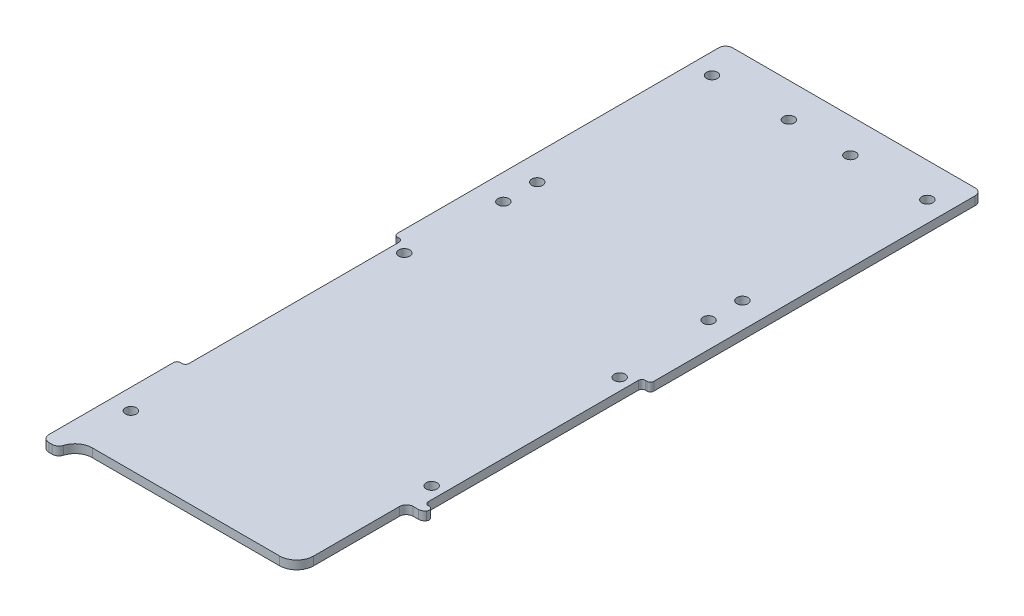
SolidWorks part; units mm, degrees
ref_plane "Front Plane" through (0, 0, 0) normal (0, 0, 1) x (1, 0, 0)
ref_plane "Top Plane" through (0, 0, 0) normal (0, 1, 0) x (1, 0, 0)
ref_plane "Right Plane" through (0, 0, 0) normal (1, 0, 0) x (0, 0, -1)
sketch "Sketch1" plane through (0, 0, 0) normal (0, 1, 0) x (1, 0, 0)
  line L0 (-39.9997, 0) -> (-39.9997, 114.3) construction
  line L1 (-47.625, 127) -> (47.625, 127)
  line L2 (-47.625, 127) -> (-47.625, -127)
  line L3 (-47.625, -127) -> (47.625, -127)
  line L4 (47.625, 127) -> (47.625, -127)
  line L5 (-47.625, 127) -> (47.625, -127) construction
  line L6 (-47.625, -127) -> (47.625, 127) construction
  line L7 (0, 0) -> (0, 127) construction
  line L8 (-39.9997, 0) -> (-39.9997, -101.6) construction
  line L9 (-39.9997, 0) -> (0, 0) construction
  line L10 (-41.275, -127) -> (-41.275, -120.65)
  line L11 (-41.275, -120.65) -> (41.275, -120.65)
  line L12 (41.275, -120.65) -> (41.275, -127)
  line L13 (-39.9997, 114.3) -> (-11.4247, 114.3) construction
  line L14 (39.9997, 114.3) -> (11.4247, 114.3) construction
  circle A0 centre (-39.9997, 114.3) radius 2.032
  circle A1 centre (-39.9997, 0) radius 2.032
  circle A2 centre (-39.9997, -101.6) radius 2.032
  circle A3 centre (39.9997, -101.6) radius 2.032
  circle A4 centre (39.9997, 0) radius 2.032
  circle A5 centre (39.9997, 114.3) radius 2.032
  circle A6 centre (-11.4247, 114.3) radius 2.032
  circle A7 centre (11.4247, 114.3) radius 2.032
  circle A8 centre (-39.9997, -69.85) radius 2.032
  circle A9 centre (39.9997, -69.85) radius 2.032
  point P0 (0, 0)
  dimension "D4" = 4.064
  dimension "D10" = 28.575
  dimension "D1" = 95.25
  dimension "D2" = 254
  dimension "D3" = 7.6253
  dimension "D5" = 12.7
  dimension "D6" = 25.4
  dimension "D7" = 6.35
  dimension "D8" = 6.35
  dimension "D9" = 6.35
  dimension "D11" = 69.85
extrude "Boss-Extrude1" add sketch "Sketch1" along normal blind 3.175 contours L4 L1 L2 L3 A4 A0 A1 A2 A3 A5 | A8 | A3 region at (0, 0, -2.6944) region at (39.9997, 0, 101.6) region at (-39.9997, 0, 69.85)
fillet "Fillet1" radius 2.54 4 edges at (-47.625, 1.5875, -127) (47.625, 1.5875, -127) (47.625, 1.5875, 127) (-47.625, 1.5875, 127)
fillet "Fillet2" radius 2.54 2 edges at (41.275, 1.5875, 127) (-41.275, 1.5875, 127)
fillet "Fillet3" radius 6.35 2 edges at (41.275, 1.5875, 120.65) (-41.275, 1.5875, 120.65)
sketch "Sketch2" plane through (0, 0, 0) normal (0, -1, 0) x (1, 0, 0)
  line L1 (43.815, 127) -> (45.085, 127) construction
  line L2 (40.6451, 123.5787) -> (40.6451, 79.8881)
  line L3 (40.6451, 79.8881) -> (47.625, 79.8881)
  line L11 (47.625, -124.46) -> (47.625, 124.46) construction
  line L12 (43.815, 127) -> (45.085, 127)
  line L13 (47.625, 79.8881) -> (47.625, 124.46)
  arc A0 (35.2956, 120.65) -> (41.3809, 125.1857) centre (35.2956, 127) ccw construction
  arc A1 (43.815, 127) -> (41.3809, 125.1857) centre (43.815, 124.46) ccw construction
  arc A2 (47.625, 124.46) -> (45.085, 127) centre (45.085, 124.46) ccw construction
  arc A3 (40.6451, 123.5787) -> (41.3809, 125.1857) centre (35.2956, 127) ccw
  arc A4 (43.815, 127) -> (41.3809, 125.1857) centre (43.815, 124.46) ccw
  arc A5 (47.625, 124.46) -> (45.085, 127) centre (45.085, 124.46) ccw
  dimension "D2" = 47.1119
  dimension "D1" = 6.9799
extrude "Cut-Extrude1" cut sketch "Sketch2" against normal through all
fillet "Fillet4" radius 6.35 1 edges at (40.6451, 1.5875, 123.5787)
fillet "Fillet5" radius 2.54 2 edges at (47.625, 1.5875, 79.8881) (40.6451, 1.5875, 79.8881)
sketch "Sketch3" plane through (0, 0, 0) normal (0, -1, 0) x (1, 0, 0)
  line L0 (-36.3061, -49.7791) -> (-39.9129, -49.7791) construction
  line L1 (-40.4209, -49.276) -> (-40.4209, -45.7043) construction
  line L2 (-35.7981, -45.7043) -> (-35.7981, -49.276) construction
  line L3 (-39.9129, -45.2013) -> (-36.3061, -45.2013) construction
  line L4 (-36.3061, -37.2027) -> (-39.9129, -37.2027) construction
  line L5 (-35.7981, -33.1279) -> (-35.7981, -36.6996) construction
  line L6 (-40.4209, -36.6996) -> (-40.4209, -33.1279) construction
  line L7 (-39.9129, -32.6249) -> (-36.3061, -32.6249) construction
  line L8 (36.2871, -32.6249) -> (39.8939, -32.6249) construction
  line L9 (40.4019, -33.1279) -> (40.4019, -36.6996) construction
  line L10 (39.8939, -37.2027) -> (36.2871, -37.2027) construction
  line L11 (35.7791, -36.6996) -> (35.7791, -33.1279) construction
  line L12 (36.2871, -45.2013) -> (39.8939, -45.2013) construction
  line L13 (35.7791, -49.276) -> (35.7791, -45.7043) construction
  line L14 (40.4019, -45.7043) -> (40.4019, -49.276) construction
  line L15 (39.8939, -49.7791) -> (36.2871, -49.7791) construction
  line L16 (-36.3061, -49.7791) -> (-39.9129, -49.7791)
  line L17 (-40.4209, -49.276) -> (-40.4209, -45.7043)
  line L18 (-35.7981, -45.7043) -> (-35.7981, -49.276)
  line L19 (-39.9129, -45.2013) -> (-36.3061, -45.2013)
  line L20 (-36.3061, -37.2027) -> (-39.9129, -37.2027)
  line L21 (-35.7981, -33.1279) -> (-35.7981, -36.6996)
  line L22 (-40.4209, -36.6996) -> (-40.4209, -33.1279)
  line L23 (-39.9129, -32.6249) -> (-36.3061, -32.6249)
  line L24 (36.2871, -32.6249) -> (39.8939, -32.6249)
  line L25 (40.4019, -33.1279) -> (40.4019, -36.6996)
  line L26 (39.8939, -37.2027) -> (36.2871, -37.2027)
  line L27 (35.7791, -36.6996) -> (35.7791, -33.1279)
  line L28 (36.2871, -45.2013) -> (39.8939, -45.2013)
  line L29 (35.7791, -49.276) -> (35.7791, -45.7043)
  line L30 (40.4019, -45.7043) -> (40.4019, -49.276)
  line L31 (39.8939, -49.7791) -> (36.2871, -49.7791)
  line L32 (-47.625, -25.836) -> (47.625, -25.836)
  line L33 (-47.625, -124.46) -> (-47.625, 124.46) construction
  line L34 (47.625, -124.46) -> (47.625, 77.3481) construction
  line L35 (0, -25.836) -> (0, -56.0686) construction
  line L1362 (-40.4209, -34.9138) -> (-35.7981, -34.9138)
  line L1857 (-38.1095, -32.6249) -> (-38.1095, -37.2027)
  line L1858 (-38.1095, -45.2013) -> (-38.1095, -49.7791)
  line L1859 (-40.4209, -47.4902) -> (-35.7981, -47.4902)
  circle A0 centre (-38.1095, -34.9138) radius 2.032
  circle A1 centre (-38.1095, -47.4902) radius 2.032
  circle A2 centre (38.1095, -47.4902) radius 2.032
  circle A3 centre (38.1095, -34.9138) radius 2.032
  ellipse E0 centre (-39.9129, -45.7043) end of major axis (-39.4049, -45.7043) minor radius 0.5031 (-39.9129, -45.2013) -> (-40.4209, -45.7043) ccw construction
  ellipse E1 centre (-39.9129, -49.276) end of major axis (-39.4049, -49.276) minor radius 0.5031 (-40.4209, -49.276) -> (-39.9129, -49.7791) ccw construction
  ellipse E6 centre (-36.3061, -49.276) end of major axis (-35.7981, -49.276) minor radius 0.5031 (-36.3061, -49.7791) -> (-35.7981, -49.276) ccw construction
  ellipse E7 centre (-36.3061, -45.7043) end of major axis (-35.7981, -45.7043) minor radius 0.5031 (-35.7981, -45.7043) -> (-36.3061, -45.2013) ccw construction
  ellipse E8 centre (-39.9129, -36.6996) end of major axis (-39.4049, -36.6996) minor radius 0.5031 (-40.4209, -36.6996) -> (-39.9129, -37.2027) ccw construction
  ellipse E9 centre (-36.3061, -36.6996) end of major axis (-35.7981, -36.6996) minor radius 0.5031 (-36.3061, -37.2027) -> (-35.7981, -36.6996) ccw construction
  ellipse E10 centre (-36.3061, -33.1279) end of major axis (-35.7981, -33.1279) minor radius 0.5031 (-35.7981, -33.1279) -> (-36.3061, -32.6249) ccw construction
  ellipse E11 centre (-39.9129, -33.1279) end of major axis (-39.4049, -33.1279) minor radius 0.5031 (-39.9129, -32.6249) -> (-40.4209, -33.1279) ccw construction
  ellipse E12 centre (39.8939, -33.1279) end of major axis (40.4019, -33.1279) minor radius 0.5031 (40.4019, -33.1279) -> (39.8939, -32.6249) ccw construction
  ellipse E13 centre (36.2871, -33.1279) end of major axis (36.7951, -33.1279) minor radius 0.5031 (36.2871, -32.6249) -> (35.7791, -33.1279) ccw construction
  ellipse E14 centre (39.8939, -36.6996) end of major axis (40.4019, -36.6996) minor radius 0.5031 (39.8939, -37.2027) -> (40.4019, -36.6996) ccw construction
  ellipse E15 centre (36.2871, -36.6996) end of major axis (36.7951, -36.6996) minor radius 0.5031 (35.7791, -36.6996) -> (36.2871, -37.2027) ccw construction
  ellipse E16 centre (36.2871, -45.7043) end of major axis (36.7951, -45.7043) minor radius 0.5031 (36.2871, -45.2013) -> (35.7791, -45.7043) ccw construction
  ellipse E17 centre (36.2871, -49.276) end of major axis (36.7951, -49.276) minor radius 0.5031 (35.7791, -49.276) -> (36.2871, -49.7791) ccw construction
  ellipse E18 centre (39.8939, -45.7043) end of major axis (40.4019, -45.7043) minor radius 0.5031 (40.4019, -45.7043) -> (39.8939, -45.2013) ccw construction
  ellipse E19 centre (39.8939, -49.276) end of major axis (40.4019, -49.276) minor radius 0.5031 (39.8939, -49.7791) -> (40.4019, -49.276) ccw construction
  ellipse E20 centre (-39.9129, -45.7043) end of major axis (-39.4049, -45.7043) minor radius 0.5031 (-39.9129, -45.2013) -> (-40.4209, -45.7043) ccw
  ellipse E21 centre (-39.9129, -49.276) end of major axis (-39.4049, -49.276) minor radius 0.5031 (-40.4209, -49.276) -> (-39.9129, -49.7791) ccw
  ellipse E22 centre (-36.3061, -49.276) end of major axis (-35.7981, -49.276) minor radius 0.5031 (-36.3061, -49.7791) -> (-35.7981, -49.276) ccw
  ellipse E23 centre (-36.3061, -45.7043) end of major axis (-35.7981, -45.7043) minor radius 0.5031 (-35.7981, -45.7043) -> (-36.3061, -45.2013) ccw
  ellipse E24 centre (-39.9129, -36.6996) end of major axis (-39.4049, -36.6996) minor radius 0.5031 (-40.4209, -36.6996) -> (-39.9129, -37.2027) ccw
  ellipse E25 centre (-36.3061, -36.6996) end of major axis (-35.7981, -36.6996) minor radius 0.5031 (-36.3061, -37.2027) -> (-35.7981, -36.6996) ccw
  ellipse E26 centre (-36.3061, -33.1279) end of major axis (-35.7981, -33.1279) minor radius 0.5031 (-35.7981, -33.1279) -> (-36.3061, -32.6249) ccw
  ellipse E27 centre (-39.9129, -33.1279) end of major axis (-39.4049, -33.1279) minor radius 0.5031 (-39.9129, -32.6249) -> (-40.4209, -33.1279) ccw
  ellipse E28 centre (39.8939, -33.1279) end of major axis (40.4019, -33.1279) minor radius 0.5031 (40.4019, -33.1279) -> (39.8939, -32.6249) ccw
  ellipse E29 centre (36.2871, -33.1279) end of major axis (36.7951, -33.1279) minor radius 0.5031 (36.2871, -32.6249) -> (35.7791, -33.1279) ccw
  ellipse E30 centre (39.8939, -36.6996) end of major axis (40.4019, -36.6996) minor radius 0.5031 (39.8939, -37.2027) -> (40.4019, -36.6996) ccw
  ellipse E31 centre (36.2871, -36.6996) end of major axis (36.7951, -36.6996) minor radius 0.5031 (35.7791, -36.6996) -> (36.2871, -37.2027) ccw
  ellipse E32 centre (36.2871, -45.7043) end of major axis (36.7951, -45.7043) minor radius 0.5031 (36.2871, -45.2013) -> (35.7791, -45.7043) ccw
  ellipse E33 centre (36.2871, -49.276) end of major axis (36.7951, -49.276) minor radius 0.5031 (35.7791, -49.276) -> (36.2871, -49.7791) ccw
  ellipse E34 centre (39.8939, -45.7043) end of major axis (40.4019, -45.7043) minor radius 0.5031 (40.4019, -45.7043) -> (39.8939, -45.2013) ccw
  ellipse E35 centre (39.8939, -49.276) end of major axis (40.4019, -49.276) minor radius 0.5031 (39.8939, -49.7791) -> (40.4019, -49.276) ccw
  dimension "D2" = 4.064
extrude "Cut-Extrude2" cut sketch "Sketch3" against normal through all contours A0 | A1 | A2 | A3
sketch "Sketch4" plane through (0, 3.175, 0) normal (0, 1, 0) x (1, 0, 0)
  line L11 (-47.625, 124.46) -> (-47.625, -124.46) construction
  line L12 (-47.625, -76.835) -> (-44.45, -76.835)
  line L13 (-47.625, -76.835) -> (-47.625, 3.81)
  line L15 (-47.625, 3.81) -> (-44.45, 3.81)
  line L16 (-44.45, -76.835) -> (-44.45, 3.81)
  line L17 (47.625, 124.46) -> (47.625, -77.3481) construction
  line L18 (47.625, -76.835) -> (44.45, -76.835)
  line L19 (47.625, -76.835) -> (47.625, 3.81)
  line L20 (47.625, 3.81) -> (44.45, 3.81)
  line L45 (44.45, -76.835) -> (44.45, 3.81)
  line L47 (43.1851, -79.8881) -> (45.085, -79.8881) construction
  dimension "D1" = 3.175
  dimension "D2" = 80.645
  dimension "D3" = 3.0531
extrude "Cut-Extrude3" cut sketch "Sketch4" against normal through all and the other way through all
fillet "Fillet6" radius 1.27 8 edges at (-44.45, 1.5875, -3.81) (-47.625, 1.5875, -3.81) (-47.625, 1.5875, 76.835) (-44.45, 1.5875, 76.835) (44.45, 1.5875, 76.835) (47.625, 1.5875, 76.835) (44.45, 1.5875, -3.81) (47.625, 1.5875, -3.81)
